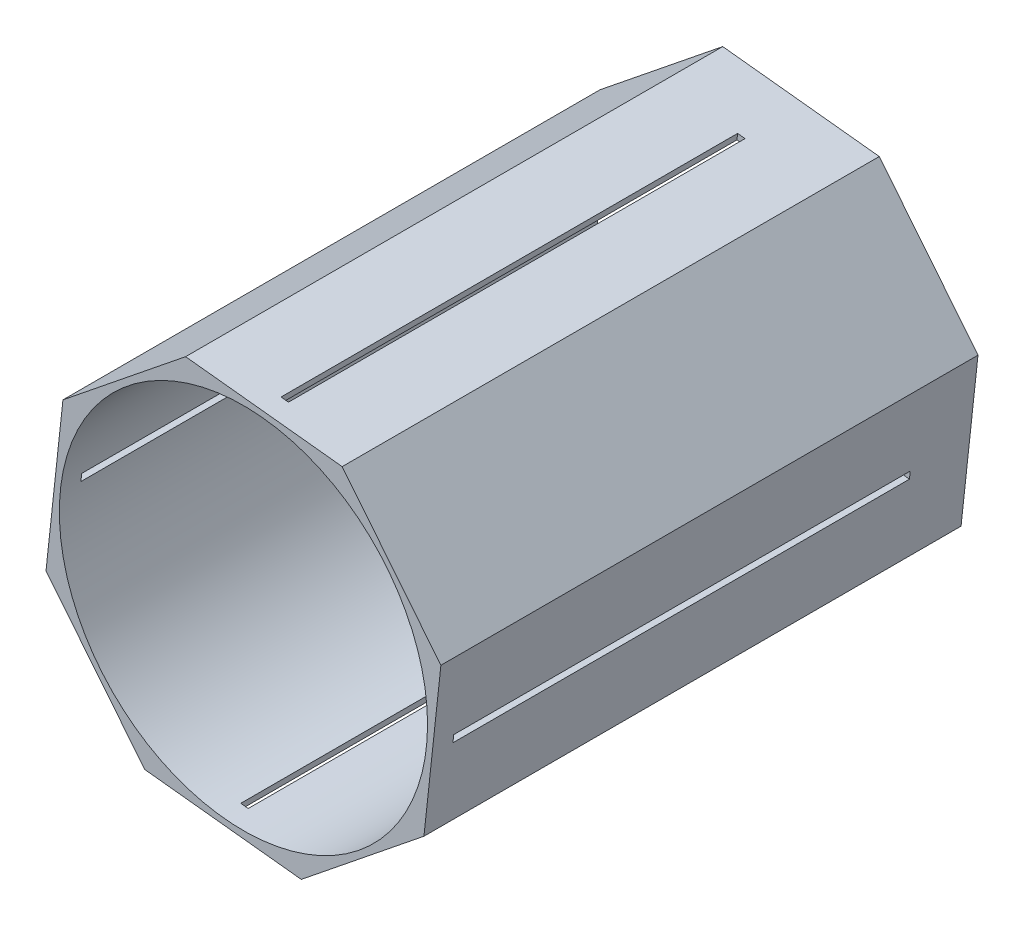
SolidWorks part; units mm, degrees
ref_plane "Front Plane" through (0, 0, 0) normal (0, 0, 1) x (1, 0, 0)
ref_plane "Top Plane" through (0, 0, 0) normal (0, 1, 0) x (1, 0, 0)
ref_plane "Right Plane" through (0, 0, 0) normal (1, 0, 0) x (0, 0, -1)
sketch "Sketch1" plane through (0, 0, 0) normal (0, 0, 1) x (1, 0, 0)
  line L0 (76.8254, -42.0166) -> (84.034, 24.6136)
  line L1 (42.0166, 76.8254) -> (-24.6136, 84.034)
  line L2 (-24.6136, 84.034) -> (-76.8254, 42.0166)
  line L3 (-76.8254, 42.0166) -> (-84.034, -24.6136)
  line L4 (-84.034, -24.6136) -> (-42.0166, -76.8254)
  line L5 (-42.0166, -76.8254) -> (24.6136, -84.034)
  line L6 (24.6136, -84.034) -> (76.8254, -42.0166)
  line L7 (84.034, 24.6136) -> (42.0166, 76.8254)
  circle A0 centre (0, 0) radius 78.359
  circle A1 centre (0, 0) radius 80.899 construction
  dimension "D1" = 156.718
  dimension "D2" = 2.54
extrude "Boss-Extrude1" add sketch "Sketch1" along normal blind 228.6
sketch "Sketch2" plane through (8.7015, 80.4297, 0) normal (0.1076, 0.9942, 0) x (0.9942, -0.1076, 0)
  line L0 (0, 0) -> (0, -228.6) construction
  line L1 (33.5095, -228.6) -> (-33.5095, -228.6) construction
  line L3 (-1.5875, -25.4) -> (1.5875, -25.4)
  line L4 (-1.5875, -25.4) -> (-1.5875, -219.71)
  line L5 (-1.5875, -219.71) -> (1.5875, -219.71)
  line L6 (1.5875, -25.4) -> (1.5875, -219.71)
  line L7 (-1.5875, -25.4) -> (1.5875, -219.71) construction
  line L8 (-1.5875, -219.71) -> (1.5875, -25.4) construction
  point P5 (0, -122.555)
  point P10 (0, -219.71)
  dimension "D1" = 8.89
  dimension "D2" = 3.175
  dimension "D3" = 194.31
extrude "Cut-Extrude1" cut sketch "Sketch2" against normal blind 203.2
sketch "Sketch5" plane through (-80.4297, 8.7015, 0) normal (-0.9942, 0.1076, 0) x (0, 0, 1)
  line L0 (0, 0) -> (228.6, 0) construction
  line L1 (0, 33.5095) -> (0, -33.5095) construction
  line L2 (228.6, 33.5095) -> (228.6, -33.5095) construction
  line L4 (25.4, -1.5875) -> (219.71, -1.5875)
  line L5 (25.4, -1.5875) -> (25.4, 1.5875)
  line L6 (25.4, 1.5875) -> (219.71, 1.5875)
  line L7 (219.71, -1.5875) -> (219.71, 1.5875)
  line L8 (25.4, -1.5875) -> (219.71, 1.5875) construction
  line L9 (25.4, 1.5875) -> (219.71, -1.5875) construction
  point P6 (122.555, 0)
  point P11 (219.71, 0)
  dimension "D1" = 8.89
  dimension "D2" = 3.175
  dimension "D3" = 194.31
extrude "Cut-Extrude2" cut sketch "Sketch5" against normal blind 203.2
